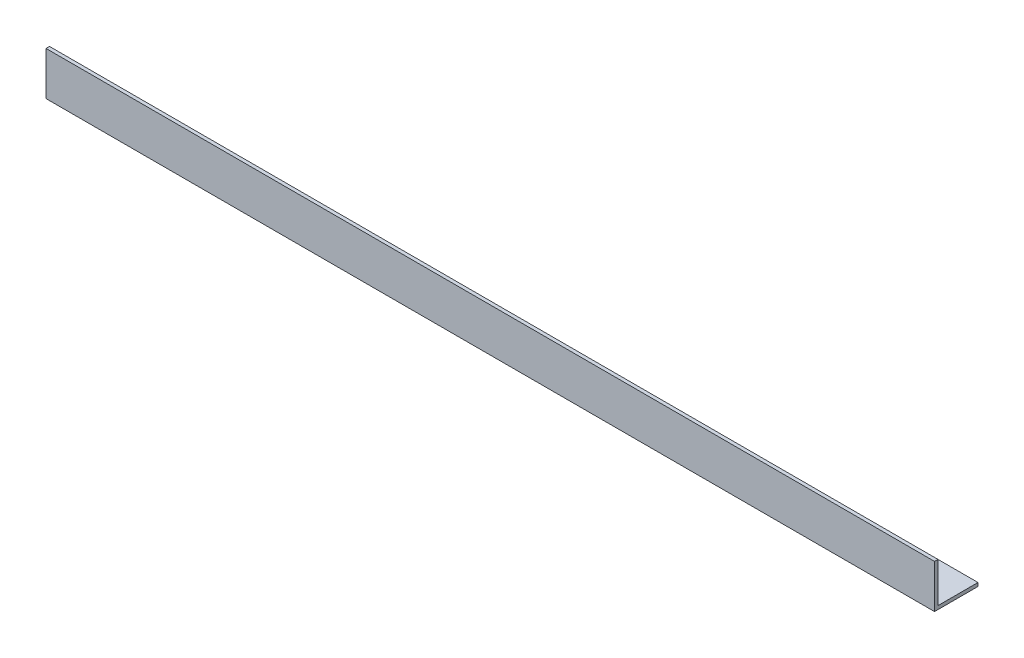
SolidWorks part; units mm, degrees
ref_plane "Спереди" through (0, 0, 0) normal (0, 0, 1) x (1, 0, 0)
ref_plane "Сверху" through (0, 0, 0) normal (0, 1, 0) x (1, 0, 0)
ref_plane "Справа" through (0, 0, 0) normal (1, 0, 0) x (0, 0, -1)
sketch "Эскиз1" plane through (0, 0, 0) normal (1, 0, 0) x (0, 0, -1)
  line L0 (0, 25) -> (0, 0)
  line L1 (0, 0) -> (25, 0)
extrude "Вытянуть-Тонкостенный1" add sketch "Эскиз1" along normal blind 511 thin thin type one direction reverse wall 2
